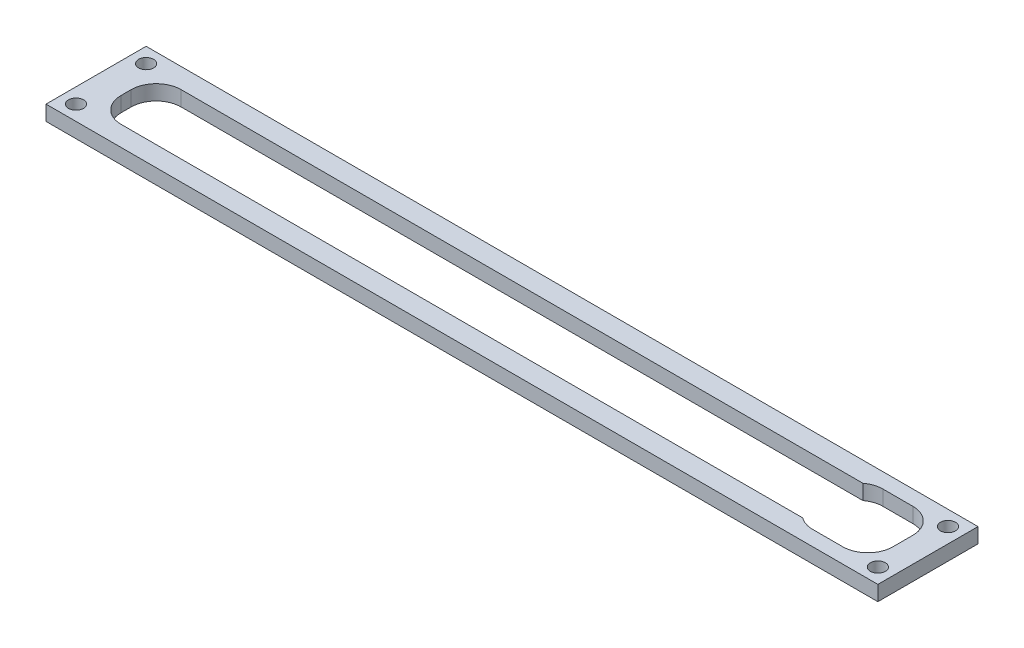
SolidWorks part; units mm, degrees
ref_plane "Front Plane" through (0, 0, 0) normal (0, 0, 1) x (1, 0, 0)
ref_plane "Top Plane" through (0, 0, 0) normal (0, 1, 0) x (1, 0, 0)
ref_plane "Right Plane" through (0, 0, 0) normal (1, 0, 0) x (0, 0, -1)
sketch "Sketch1" plane through (0, 0, 0) normal (0, 1, 0) x (1, 0, 0)
  line L0 (83.0799, 20) -> (83.0799, 0) construction
  line L1 (0, 0) -> (166.1597, 0)
  line L2 (0, 0) -> (0, 20)
  line L3 (0, 20) -> (166.1597, 20)
  line L4 (166.1597, 0) -> (166.1597, 20)
  line L5 (0, 10) -> (166.1597, 10) construction
  line L6 (83.0799, 16) -> (83.0799, 4) construction
  line L7 (6, 16) -> (160.1597, 16)
  line L8 (6, 16) -> (6, 4)
  line L9 (6, 4) -> (160.1597, 4)
  line L10 (160.1597, 16) -> (160.1597, 4)
  line L11 (6, 10) -> (160.1597, 10) construction
  circle A0 centre (3, 17) radius 1.5
  circle A1 centre (3, 3) radius 1.5
  circle A2 centre (163.1597, 3) radius 1.5
  circle A3 centre (163.1597, 17) radius 1.5
  point P17 (83.0799, 10)
  point P18 (83.0799, 10)
  dimension "D7" = 3
  dimension "D1" = 166.1597
  dimension "D2" = 20
  dimension "D3" = 154.1597
  dimension "D4" = 12
  dimension "D5" = 3
  dimension "D6" = 3
extrude "Boss-Extrude1" add sketch "Sketch1" along normal blind 3
sketch "Sketch2" plane through (0, 3, 0) normal (0, 1, 0) x (1, 0, 0)
  line L0 (92, 10) -> (-49908, 10) construction
  line L1 (160.1597, 4) -> (160.1597, 16) construction
  line L2 (147.1597, 17) -> (147.1597, 16)
  line L5 (160.1597, 16) -> (6, 16) construction
  line L6 (154.1597, 17) -> (154.1597, 3) construction
  line L7 (147.1597, 17) -> (161.1597, 17)
  line L9 (147.1597, 3) -> (161.1597, 3)
  line L10 (161.1597, 17) -> (161.1597, 3)
  line L12 (147.1597, 16) -> (160.1597, 16)
  line L13 (160.1597, 16) -> (160.1597, 4)
  line L14 (160.1597, 4) -> (147.1597, 4)
  line L15 (6, 4) -> (160.1597, 4) construction
  line L16 (147.1597, 4) -> (147.1597, 3)
  point P4 (160.1597, 10)
  point P23 (154.1597, 10)
  dimension "D1" = 1
  dimension "D2" = 14
  dimension "D3" = 14
extrude "Cut-Extrude1" cut sketch "Sketch2" against normal through all
fillet "Fillet1" radius 5 6 edges at (161.1597, 1.5, -17) (161.1597, 1.5, -3) (147.1597, 1.5, -17) (147.1597, 1.5, -3) (6, 1.5, -4) (6, 1.5, -16)
equation "\"TrackLength\"= ( ( \"n\" * 28 ) ) / cos ( \"MountAngle\" ) - ( 2 * \"x\" )"
equation "\"D1@Sketch1\"=\"TrackLength\""
equation "\"TrackWidth\"= \"MarbleTrackWidth\" + ( 2 * 4 )"
equation "\"D2@Sketch1\"=\"TrackWidth\""
equation "\"MarbleTrackWidth\"= \"MarbleWidth\" - 1"
equation "\"MarbleTrackLength\"= \"TrackLength\" - ( 2 * 6 )"
equation "\"D3@Sketch1\"=\"MarbleTrackLength\""
equation "\"D4@Sketch1\"=\"MarbleTrackWidth\""
equation "\"MarbleWidth\"= 13"
equation "\"n\"= 6"
equation "\"MountAngle\"= 10"
equation "\"x\"= 14 / cos ( \"MountAngle\" ) - 12"
